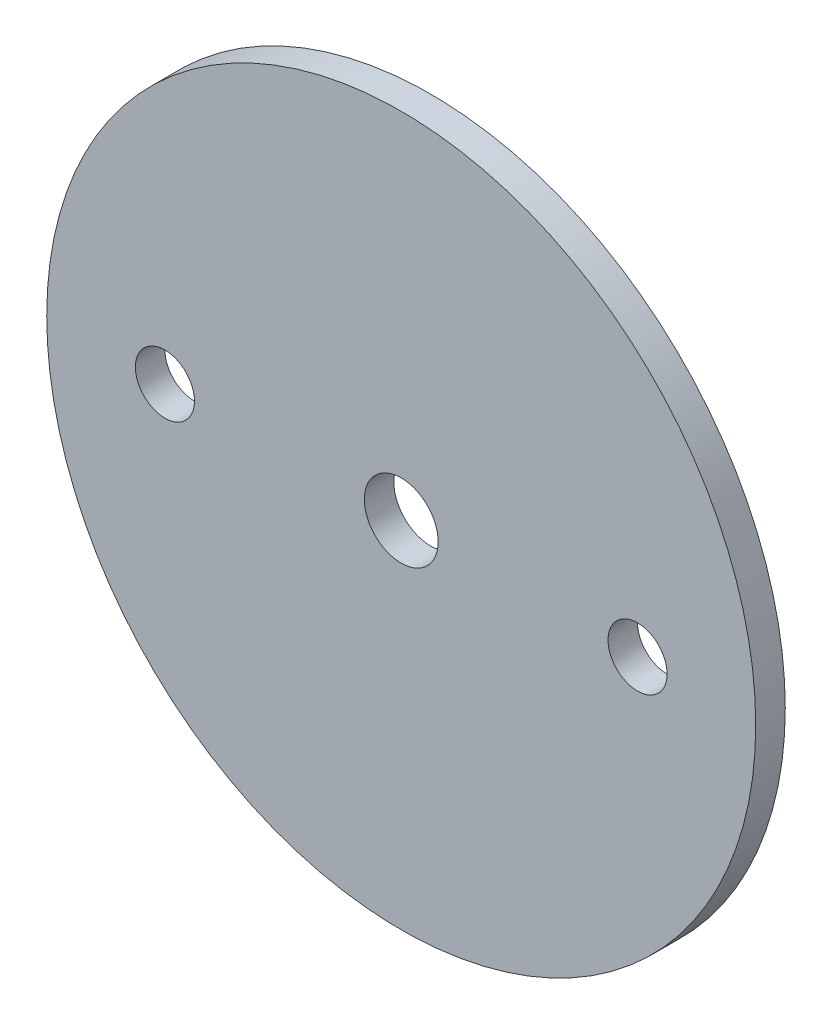
SolidWorks part; units mm, degrees
ref_plane "Front Plane" through (0, 0, 0) normal (0, 0, 1) x (1, 0, 0)
ref_plane "Top Plane" through (0, 0, 0) normal (0, 1, 0) x (1, 0, 0)
ref_plane "Right Plane" through (0, 0, 0) normal (1, 0, 0) x (0, 0, -1)
sketch "Sketch1" plane through (0, 0, 0) normal (0, 0, 1) x (1, 0, 0)
  circle A0 centre (0, 0) radius 38.1
extrude "Boss-Extrude1" add sketch "Sketch1" along normal mid plane 3.175
sketch "Sketch2" plane through (0, 0, 1.5875) normal (0, 0, 1) x (1, 0, 0)
  line L0 (-1000, 0) -> (49000, 0) construction
  line L1 (0, -1000) -> (0, 49000) construction
  point P4 (25.4, 0)
  point P5 (-25.4, 0)
  dimension "D2" = 50.8
  dimension "D1" = 25.4
hole_wizard "1/4 (0.25) Diameter Hole1" positions "Sketch2" profile "Sketch3" hole size "1/4" standard "ANSI Inch" end condition through all
sketch "Sketch3" plane through (-25.4, 0, 1.5875) normal (1, 0, 0) x (0, -1, 0)
  line L0 (0, 0) -> (0, 3.175)
  line L1 (0, 3.175) -> (3.175, 3.175)
  line L2 (3.175, 3.175) -> (3.175, 0)
  line L5 (3.175, 0) -> (0, 0)
  line L11 (0, -6.35) -> (0, 107.95) construction
  dimension "Thru Hole Dia." = 6.35
  dimension "Thru Hole Depth" = 3.175
sketch "Sketch4" plane through (0, 0, 1.5875) normal (0, 0, 1) x (1, 0, 0)
  point P0 (0, 0)
hole_wizard "5/16 (0.3125) Diameter Hole1" positions "Sketch4" profile "Sketch5" hole size "5/16" standard "ANSI Inch"
sketch "Sketch5" plane through (0, 0, 1.5875) normal (1, 0, 0) x (0, -1, 0)
  line L0 (0, 0) -> (0, 3.302)
  line L1 (0, 3.302) -> (3.9687, 3.302)
  line L2 (3.9687, 3.302) -> (3.9688, 0)
  line L5 (3.9688, 0) -> (0, 0)
  line L10 (0, 3.302) -> (-3.9688, 3.302) construction
  line L11 (0, -6.35) -> (0, 107.95) construction
  dimension "Hole Dia." = 7.9375
  dimension "Hole Depth" = 3.302
  dimension "Drill Angle" = 180
equation "\"AIRFRAME_OD\"= 3.091in"
equation "\"AIRFRAME_ID\"= 3.00in"
equation "\"FLAT_T\"= 0.125in"
equation "\"NOSE_EXP_L\"= 3.5in"
equation "\"NOSE_SHOULDER_L\"= 5in"
equation "\"MAIN_L\"= 30in"
equation "\"RECO_COUP_L\"= 6in"
equation "\"RECO_SWITCH_L\"= 1.5in"
equation "\"DROGUE_L\"= 14in"
equation "\"ATS_FORE_COUP_L\"= 4in"
equation "\"ATS_AFT_COUP_L\"= 4in"
equation "\"LOWER_L\"= 16in"
equation "\"FIN_N\"= 4"
equation "\"CR_AFT_X\"= 0.5in"
equation "\"CR_FORE_X\"= 6in"
equation "\"FIN_ROOT\"= 5in"
equation "\"FIN_X\"= 0.75in"
equation "\"MOTOR_OD\"= 2.25in"
equation "\"MOTOR_ID\"= 2.126in"
equation "\"COUPLER_OD\"= 2.998in"
equation "\"COUPLER_ID\"= 2.875in"
equation "\"D1@Sketch1\"=\"AIRFRAME_ID\""
equation "\"D1@Boss-Extrude1\"=\"FLAT_T\""
equation "\"RECO_ROD_X\"= 1.5in"
equation "\"ATS_ROD_X\"= 2in"
equation "\"D2@Sketch2\"=\"ATS_ROD_X\""
